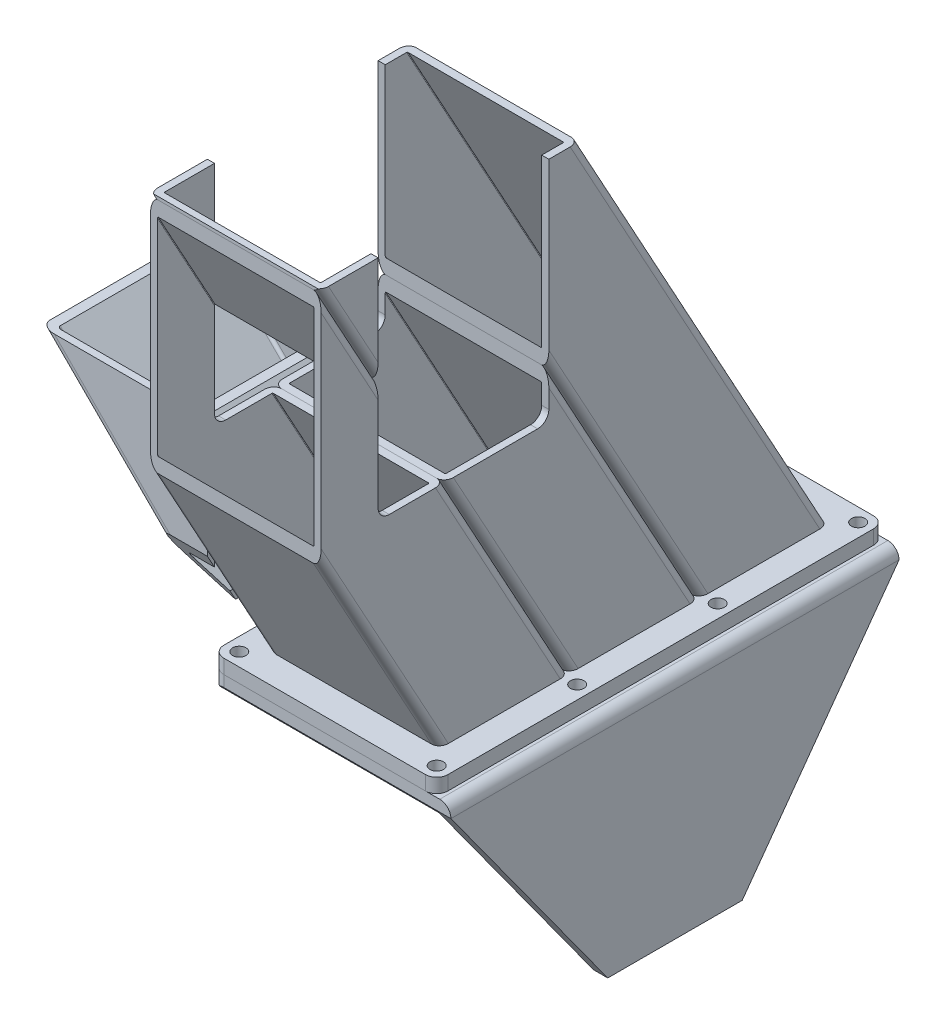
SolidWorks part; units mm, degrees
ref_plane "Front Plane" through (0, 0, 0) normal (0, 0, 1) x (1, 0, 0)
ref_plane "Top Plane" through (0, 0, 0) normal (0, 1, 0) x (1, 0, 0)
ref_plane "Right Plane" through (0, 0, 0) normal (1, 0, 0) x (0, 0, -1)
sketch "Sketch1" plane through (0, 0, 0) normal (1, 0, 0) x (0, 0, -1)
  line L10 (-138.4, 216.11) -> (-138.4, 119.405)
  line L11 (-143.4, 114.405) -> (-209.6, 114.405)
  line L12 (-214.6, 119.405) -> (-214.6, 216.11)
  line L14 (-236.0457, 96.4954) -> (-202.1426, 50.9302)
  line L15 (-240, 216.11) -> (-240, 108.4343)
  line L16 (-125.7, 216.11) -> (-240, 216.11)
  line L17 (-3.9543, 52.4853) -> (-125.7, 216.11)
  line L18 (0, 0) -> (0, 40.5465)
  line L19 (-198.1883, 0) -> (0, 0)
  line L20 (-198.1883, 38.9913) -> (-198.1883, 0)
  arc A5 (-143.4, 114.405) -> (-138.4, 119.405) centre (-143.4, 119.405) ccw
  arc A6 (-240, 108.4343) -> (-236.0457, 96.4954) centre (-220, 108.4343) ccw
  arc A7 (0, 40.5465) -> (-3.9543, 52.4853) centre (-20, 40.5465) ccw
  arc A8 (-198.1883, 38.9913) -> (-202.1426, 50.9302) centre (-218.1883, 38.9913) ccw
  arc A9 (-214.6, 119.405) -> (-209.6, 114.405) centre (-209.6, 119.405) ccw
sketch "Sketch2" plane through (0, 0, 0) normal (1, 0, 0) x (0, 0, -1)
  line L0 (-140.0309, 243.7308) -> (5.0037, -21.0259) construction
  line L1 (-209.1547, 264.1777) -> (-48.2541, -29.5419) construction
  line L2 (-277.3065, 282.8503) -> (-105.2948, -31.1523) construction
  line L3 (-300.7802, 219.9643) -> (-155.523, -45.1987) construction
  dimension "D1" = 50.8
  dimension "D2" = 50.8
  dimension "D3" = 50.8
sketch3d "3DSketch1"
  line L0 (0, 243.7308, 140.0309) -> (220.1194, 243.7308, 140.0309)
  line L1 (0, 243.7308, 140.0309) -> (0, 116.1723, 372.8854)
  line L2 (0, 243.7308, 140.0309) -> (0, -21.0259, -5.0037) construction
ref_plane "Plane1" through (0, 246.4757, 135.0202) normal (0, -0.877, -0.4804) x (-1, 0, 0)
sketch "Sketch3" plane through (0, 246.4757, 135.0202) normal (0, -0.877, -0.4804) x (-1, 0, 0)
  line L0 (-3.175, -9.2133) -> (-3.175, -53.0133)
  line L1 (-3.5, -5.7133) -> (-72.7, -5.7133)
  line L2 (0, -9.2133) -> (0, -53.0133)
  line L3 (-3.5, -56.5133) -> (-72.7, -56.5133)
  line L4 (-76.2, -9.2133) -> (-76.2, -53.0133)
  line L5 (0, -5.7133) -> (-76.2, -56.5133) construction
  line L6 (0, -56.5133) -> (-76.2, -5.7133) construction
  line L7 (-3.5, -53.3383) -> (-72.7, -53.3383)
  line L8 (-73.025, -9.2133) -> (-73.025, -53.0133)
  line L9 (-3.5, -8.8883) -> (-72.7, -8.8883)
  line L10 (0, -5.7133) -> (0, -271.2173) construction
  line L11 (0, -5.7133) -> (-220.1194, -5.7133) construction
  arc A0 (-72.7, -56.5133) -> (-76.2, -53.0133) centre (-72.7, -53.0133) cw
  arc A1 (0, -53.0133) -> (-3.5, -56.5133) centre (-3.5, -53.0133) cw
  arc A2 (-3.5, -5.7133) -> (0, -9.2133) centre (-3.5, -9.2133) cw
  arc A3 (-72.7, -5.7133) -> (-76.2, -9.2133) centre (-72.7, -9.2133) ccw
  arc A4 (-3.175, -53.0133) -> (-3.5, -53.3383) centre (-3.5, -53.0133) cw
  arc A5 (-72.7, -53.3383) -> (-73.025, -53.0133) centre (-72.7, -53.0133) cw
  arc A6 (-72.7, -8.8883) -> (-73.025, -9.2133) centre (-72.7, -9.2133) ccw
  arc A7 (-3.5, -8.8883) -> (-3.175, -9.2133) centre (-3.5, -9.2133) cw
  point P0 (-38.1, -31.1133)
  dimension "D3" = 3.5
  dimension "D1" = 76.2
  dimension "D2" = 50.8
  dimension "D4" = 3.175
extrude "Boss-Extrude1" add sketch "Sketch3" along normal blind 328 and the other way blind 70
mirror "Mirror1" about plane through (3.5, 280.7165, 218.2147) normal (0, -0.4804, 0.877) of bodies 101
mirror "Mirror2" about plane through (3.5, 256.3102, 262.7677) normal (0, -0.4804, 0.877) of bodies 102
sketch "Sketch4" plane through (0, 0, 0) normal (1, 0, 0) x (0, 0, -1)
  line L0 (-198.1883, 0) -> (0, 0) construction
  line L1 (89.1188, -119.5204) -> (-223.8982, -119.5204)
  line L2 (89.1188, -119.5204) -> (89.1188, 12.7)
  line L3 (89.1188, 12.7) -> (-223.8982, 12.7)
  line L4 (-223.8982, -119.5204) -> (-223.8982, 12.7)
  line L5 (-214.6, 119.405) -> (-214.6, 216.11) construction
  line L6 (-143.4, 114.405) -> (-209.6, 114.405) construction
  line L7 (-138.4, 216.11) -> (-138.4, 119.405) construction
  line L8 (-214.6, 119.405) -> (-214.6, 216.11)
  line L9 (-143.4, 114.405) -> (-209.6, 114.405)
  line L10 (-138.4, 216.11) -> (-138.4, 119.405)
  line L11 (-138.4, 216.11) -> (-93.9894, 216.11)
  line L12 (-93.9894, 216.11) -> (-93.9894, 355.0563)
  line L13 (-93.9894, 355.0563) -> (-353.4588, 355.0563)
  line L14 (-353.4588, 355.0563) -> (-353.4588, 57.1829)
  line L15 (-353.4588, 57.1829) -> (-240, 57.1829)
  line L16 (-240, 57.1829) -> (-240, 216.11)
  line L17 (-240, 216.11) -> (-214.6, 216.11)
  arc A0 (-214.6, 119.405) -> (-209.6, 114.405) centre (-209.6, 119.405) ccw construction
  arc A1 (-143.4, 114.405) -> (-138.4, 119.405) centre (-143.4, 119.405) ccw construction
  arc A2 (-214.6, 119.405) -> (-209.6, 114.405) centre (-209.6, 119.405) ccw
  arc A3 (-143.4, 114.405) -> (-138.4, 119.405) centre (-143.4, 119.405) ccw
  dimension "D1" = 12.7
extrude "Cut-Extrude2" cut sketch "Sketch4" against normal blind 328 and the other way through all
sketch "Sketch5" plane through (0, 12.7, 0) normal (0, -1, 0) x (1, 0, 0)
  line L0 (38.1, 100.3558) -> (38.1, 187.2401) construction
  line L1 (88.1, 200.3558) -> (-11.9, 200.3558)
  line L2 (88.1, 200.3558) -> (88.1, 0.3558)
  line L3 (88.1, 0.3558) -> (-11.9, 0.3558)
  line L4 (-11.9, 200.3558) -> (-11.9, 0.3558)
  line L5 (88.1, 200.3558) -> (-11.9, 0.3558) construction
  line L6 (88.1, 0.3558) -> (-11.9, 200.3558) construction
  line L7 (3.5, 187.2401) -> (72.7, 187.2401) construction
  line L8 (38.1, 187.2401) -> (38.1, 200.3558) construction
  line L9 (38.1, 100.3558) -> (38.1, 13.4715) construction
  line L10 (72.7, 13.4715) -> (3.5, 13.4715) construction
  line L11 (38.1, 13.4715) -> (38.1, 0.3558) construction
  line L12 (38.1, 125.697) -> (38.1, 75.0145) construction
  line L13 (3.5, 125.697) -> (72.7, 125.697) construction
  line L14 (72.7, 75.0145) -> (3.5, 75.0145) construction
  line L15 (-5.95, 163.0558) -> (-11.9, 163.0558) construction
  line L16 (-5.95, 194.4058) -> (82.15, 194.4058) construction
  line L17 (-5.95, 194.4058) -> (-5.95, 131.7058) construction
  line L18 (-5.95, 131.7058) -> (82.15, 131.7058) construction
  line L19 (82.15, 194.4058) -> (82.15, 131.7058) construction
  line L20 (82.15, 163.0558) -> (88.1, 163.0558) construction
  line L21 (77.1422, 194.4058) -> (77.1422, 200.3558) construction
  line L22 (38.1, 100.3558) -> (82.15, 100.3558) construction
  line L23 (82.15, 100.3558) -> (82.15, 131.7058) construction
  line L24 (82.15, 69.0058) -> (103.5998, 69.0058) construction
  line L25 (103.5998, 131.7058) -> (103.5998, 194.4058) construction
  line L26 (85.125, 131.7058) -> (82.15, 131.7058) construction
  line L27 (82.15, 163.0558) -> (76.2, 163.0558) construction
  line L28 (76.2, 133.308) -> (76.2, 183.2494) construction
  line L29 (38.1, 100.3558) -> (165.2507, 100.3558) construction
  line L30 (103.5998, 194.4058) -> (82.15, 194.4058) construction
  line L31 (82.15, 131.7058) -> (103.5998, 131.7058) construction
  line L32 (103.5998, 69.0058) -> (103.5998, 131.7058) construction
  circle A0 centre (-5.95, 194.4058) radius 3
  circle A1 centre (82.15, 194.4058) radius 3
  circle A2 centre (-5.95, 131.7058) radius 3
  circle A3 centre (82.15, 131.7058) radius 3
  circle A4 centre (-5.95, 69.0058) radius 3
  circle A5 centre (-5.95, 6.3058) radius 3
  circle A6 centre (82.15, 6.3058) radius 3
  circle A7 centre (82.15, 69.0058) radius 3
  point P0 (38.1, 100.3558)
  dimension "D3" = 6
  dimension "D1" = 100
  dimension "D2" = 200
extrude "Boss-Extrude2" add sketch "Sketch5" along normal blind 6.35 separate body
fillet "Fillet1" radius 5 4 edges at (-11.9, 9.525, 0.3558) (88.1, 9.525, 200.3558) (-11.9, 9.525, 200.3558) (88.1, 9.525, 0.3558)
sketch "Sketch6" plane through (0, 0, 0) normal (0, 0, 1) x (1, 0, 0)
  line L0 (3.5, 115.6203) -> (-48.2891, 167.4093) construction
  line L1 (72.7, 115.6203) -> (3.5, 115.6203) construction
  dimension "D1" = 45
ref_plane "Plane2" through (-57.2025, 57.2025, 0) normal (-0.7071, 0.7071, 0) x (0.7071, 0.7071, 0)
sketch "Sketch7" plane through (-57.2025, 57.2025, 0) normal (-0.7071, 0.7071, 0) x (0.7071, 0.7071, 0)
  line L0 (31.2716, -142.9) -> (31.2716, -210.1)
  line L1 (32.5966, -138.4) -> (74.3966, -138.4)
  line L2 (28.0966, -142.9) -> (28.0966, -210.1)
  line L3 (32.5966, -214.6) -> (74.3966, -214.6)
  line L4 (78.8966, -142.9) -> (78.8966, -210.1)
  line L5 (28.0966, -138.4) -> (78.8966, -214.6) construction
  line L6 (28.0966, -214.6) -> (78.8966, -138.4) construction
  line L7 (32.5966, -211.425) -> (74.3966, -211.425)
  line L8 (75.7216, -142.9) -> (75.7216, -210.1)
  line L9 (32.5966, -141.575) -> (74.3966, -141.575)
  line L10 (106.5416, -138.4) -> (106.5416, -214.6) construction
  line L11 (152.8128, -138.4) -> (84.4321, -138.4) construction
  line L12 (84.4321, -214.6) -> (152.8128, -214.6) construction
  line L13 (53.4966, -176.5) -> (106.5416, -176.5) construction
  line L14 (80.8966, -143.4) -> (80.8966, -209.6) construction
  arc A0 (28.0966, -210.1) -> (32.5966, -214.6) centre (32.5966, -210.1) ccw
  arc A1 (74.3966, -214.6) -> (78.8966, -210.1) centre (74.3966, -210.1) ccw
  arc A2 (74.3966, -138.4) -> (78.8966, -142.9) centre (74.3966, -142.9) cw
  arc A3 (32.5966, -138.4) -> (28.0966, -142.9) centre (32.5966, -142.9) ccw
  arc A4 (31.2716, -210.1) -> (32.5966, -211.425) centre (32.5966, -210.1) ccw
  arc A5 (74.3966, -211.425) -> (75.7216, -210.1) centre (74.3966, -210.1) ccw
  arc A6 (74.3966, -141.575) -> (75.7216, -142.9) centre (74.3966, -142.9) cw
  arc A7 (32.5966, -141.575) -> (31.2716, -142.9) centre (32.5966, -142.9) ccw
  point P0 (53.4966, -176.5)
  dimension "D3" = 4.5
  dimension "D1" = 50.8
  dimension "D2" = 76.2
  dimension "D5" = 2
  dimension "D4" = 3.175
extrude "Boss-Extrude3" add sketch "Sketch7" against normal up to surface and the other way up to surface separate body up to face at (0, 107.1795, 203.1769) other way up to face at (38.1, 114.405, 169.3713)
mirror "Mirror3" about plane through (0, 6.35, 0) normal (0, 1, 0) of bodies 108
sketch "Sketch8" plane through (76.2, 0, 0) normal (1, 0, 0) x (0, 0, -1)
  line L0 (-240, 109.0117) -> (-187.2401, 12.7) construction
  line L1 (-240, 109.0117) -> (-187.2401, 12.7)
  line L2 (-187.2401, 12.7) -> (-240, 12.7)
  line L3 (-240, 12.7) -> (-240, 109.0117)
extrude "Cut-Extrude3" cut sketch "Sketch8" against normal blind 166.35
other "DeleteFace1" face at (86.1178, 3.175, 2.338) face at (86.1178, 3.175, 198.3735) and patch yes
sketch "Sketch9" plane through (0, 0, 0.3558) normal (0, 0, -1) x (-1, 0, 0)
  line L1 (-88.1, 6.35) -> (-94.45, 6.35)
  line L2 (-88.1, 6.35) -> (-88.1, -95.25)
  line L3 (-88.1, -95.25) -> (-94.45, -95.25)
  line L4 (-94.45, 6.35) -> (-94.45, -95.25)
  dimension "D1" = 101.6
  dimension "D2" = 6.35
extrude "Boss-Extrude4" add sketch "Sketch9" against normal up to surface (200 mm away) up to face at (40.6, 3.175, 200.3558)
fillet "Fillet2" radius 5 1 edges at (94.45, 6.35, 100.3558)
sketch "Sketch10" plane through (94.45, 0, 0) normal (1, 0, 0) x (0, 0, -1)
  line L0 (-100.3558, -95.25) -> (-100.3558, 1.35) construction
  line L1 (-200.3558, -95.25) -> (-0.3558, -95.25) construction
  line L2 (-0.3558, 1.35) -> (-200.3558, 1.35) construction
  line L3 (-200.3558, 1.35) -> (-200.3558, -95.25)
  line L4 (-200.3558, -95.25) -> (-130.3558, -95.25)
  line L5 (-130.3558, -95.25) -> (-200.3558, 1.35)
  line L6 (-70.3558, -95.25) -> (-0.3558, 1.35)
  line L7 (-0.3558, -95.25) -> (-70.3558, -95.25)
  line L8 (-0.3558, 1.35) -> (-0.3558, -95.25)
  dimension "D1" = 60
extrude "Cut-Extrude4" cut sketch "Sketch10" against normal blind 186.35
